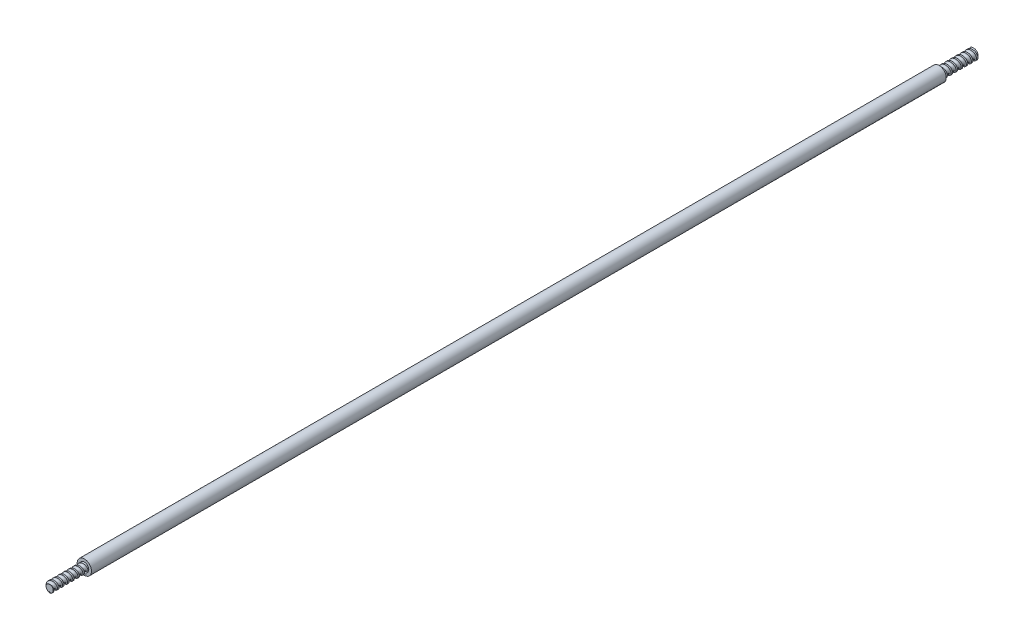
SolidWorks part; units mm, degrees
ref_plane "Front Plane" through (0, 0, 0) normal (0, 0, 1) x (1, 0, 0)
ref_plane "Top Plane" through (0, 0, 0) normal (0, 1, 0) x (1, 0, 0)
ref_plane "Right Plane" through (0, 0, 0) normal (1, 0, 0) x (0, 0, -1)
sketch "Sketch1" plane through (0, 0, 0) normal (0, 0, 1) x (1, 0, 0)
  circle A0 centre (0, 0) radius 1.27
  dimension "D1" = 2.54
extrude "Boss-Extrude1" add sketch "Sketch1" against normal blind 152.146
sketch "Sketch2" plane through (0, 0, 0) normal (0, 0, 1) x (1, 0, 0)
  circle A0 centre (0, 0) radius 0.7861
extrude "Boss-Extrude2" add sketch "Sketch2" along normal blind 6.35
sketch "Sketch3" plane through (0, 0, -152.146) normal (0, 0, -1) x (-1, 0, 0)
  circle A0 centre (0, 0) radius 0.8948
extrude "Boss-Extrude3" add sketch "Sketch3" along normal blind 6.35
sketch "Sketch4" plane through (0, 0, 6.35) normal (0, 0, 1) x (1, 0, 0)
  circle A0 centre (0, 0) radius 0.7831
curve "Helix/Spiral1" pitch 0.9071 height 6.35 turns 7
sketch "Sketch61" plane through (0, 0, -158.496) normal (0, 0, -1) x (-1, 0, 0)
  circle A0 centre (0, 0) radius 0.8871
curve "Helix/Spiral2" pitch 0.9071 height 6.35 turns 7
sweep "Cut-Sweep1" cut path "Helix/Spiral1" parameters "D3"=0.635
sweep "Cut-Sweep2" cut path "Helix/Spiral2" circular profile diameter 0.635 parameters "D3"=0.635
